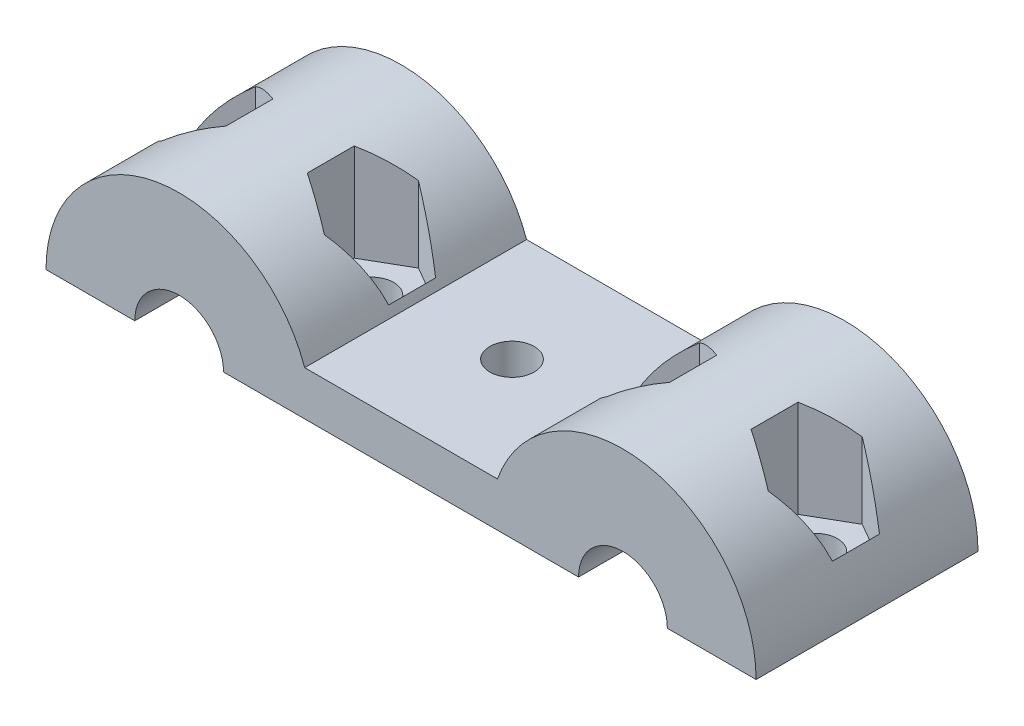
SolidWorks part; units mm, degrees
ref_plane "Спереди" through (0, 0, 0) normal (0, 0, 1) x (1, 0, 0)
ref_plane "Сверху" through (0, 0, 0) normal (0, 1, 0) x (1, 0, 0)
ref_plane "Справа" through (0, 0, 0) normal (1, 0, 0) x (0, 0, -1)
sketch "Sketch1" plane through (0, 0, 0) normal (0, 0, 1) x (1, 0, 0)
  line L0 (12, 0) -> (-12, 0)
  line L1 (0, 0) -> (0, 17.8788) construction
  line L4 (18, 0) -> (24, 0)
  line L5 (6.5147, 3) -> (-6.5147, 3)
  line L6 (-18, 0) -> (-24, 0)
  arc A1 (12, 0) -> (18, 0) centre (15, 0) cw
  arc A2 (6.5147, 3) -> (24, 0) centre (15, 0) cw
  arc A4 (-6.5147, 3) -> (-24, 0) centre (-15, 0) ccw
  arc A5 (-12, 0) -> (-18, 0) centre (-15, 0) ccw
  point P5 (8.857, 3.0019)
  point P14 (0, 3)
  point P17 (8.2918, 6)
  point P18 (-8.2918, 6)
  point P19 (0, 0)
  point P20 (0, 0)
  point P21 (0, 0)
  point P22 (0, 0)
  point P23 (5.4709, 3.0019)
  point P24 (8.5882, 4.1306)
  point P25 (16.3571, -1.2236)
  point P26 (8.4808, 3.0019)
  dimension "D1" = 3
  dimension "D3" = 6
  dimension "D4" = 3
  dimension "D2" = 30
extrude "Boss-Extrude1" add sketch "Sketch1" along normal blind 15
ref_plane "Plane1" through (0, 2, 0) normal (0, -1, 0) x (-1, 0, 0)
sketch "Sketch2" plane through (0, 2, 0) normal (0, -1, 0) x (-1, 0, 0)
  line L0 (-24, -15) -> (-6.5147, -15) construction
  line L1 (-20.5, -10.6754) -> (-17.75, -9.0877)
  line L2 (-17.75, -9.0877) -> (-17.75, -5.9123)
  line L3 (-17.75, -5.9123) -> (-20.5, -4.3246)
  line L4 (-20.5, -4.3246) -> (-23.25, -5.9123)
  line L5 (-23.25, -5.9123) -> (-23.25, -9.0877)
  line L6 (-23.25, -9.0877) -> (-20.5, -10.6754)
  line L7 (-24, -15) -> (-24, 0) construction
  circle A0 centre (-20.5, -7.5) radius 2.75 construction
  point P1 (-19.3124, -6.8814)
  dimension "D1" = 5.5
  dimension "D2" = 7.5
  dimension "D3" = 3.5
extrude "Cut-Extrude1" cut sketch "Sketch2" against normal blind 30
sketch "Sketch3" plane through (0, 2, 0) normal (0, 1, 0) x (1, 0, 0)
  line L0 (6.5147, -15) -> (24, -15) construction
  line L1 (24, -15) -> (24, 0) construction
  circle A0 centre (20.5, -7.5) radius 1.5
  dimension "D1" = 3
  dimension "D2" = 7.5
  dimension "D3" = 3.5
extrude "Cut-Extrude2" cut sketch "Sketch3" against normal blind 30
ref_axis "Axis1" through (15, 0, 15) along (0, 0, -1)
ref_plane "Plane2" through (15, 0, 0) normal (-1, 0, 0) x (0, 0, -1)
mirror "Mirror1" about plane through (15, 0, 0) normal (-1, 0, 0) of "Cut-Extrude1", "Cut-Extrude2"
mirror "Mirror2" about plane through (0, 0, 0) normal (1, 0, 0) of "Cut-Extrude1", "Cut-Extrude2", "Mirror1"
sketch "Sketch4" plane through (0, 3, 0) normal (0, 1, 0) x (1, 0, 0)
  line L0 (6.5147, -15) -> (-6.5147, -15) construction
  circle A0 centre (0, -7.5) radius 1.5
  dimension "D1" = 3
  dimension "D2" = 7.5
extrude "Cut-Extrude3" cut sketch "Sketch4" against normal blind 5
